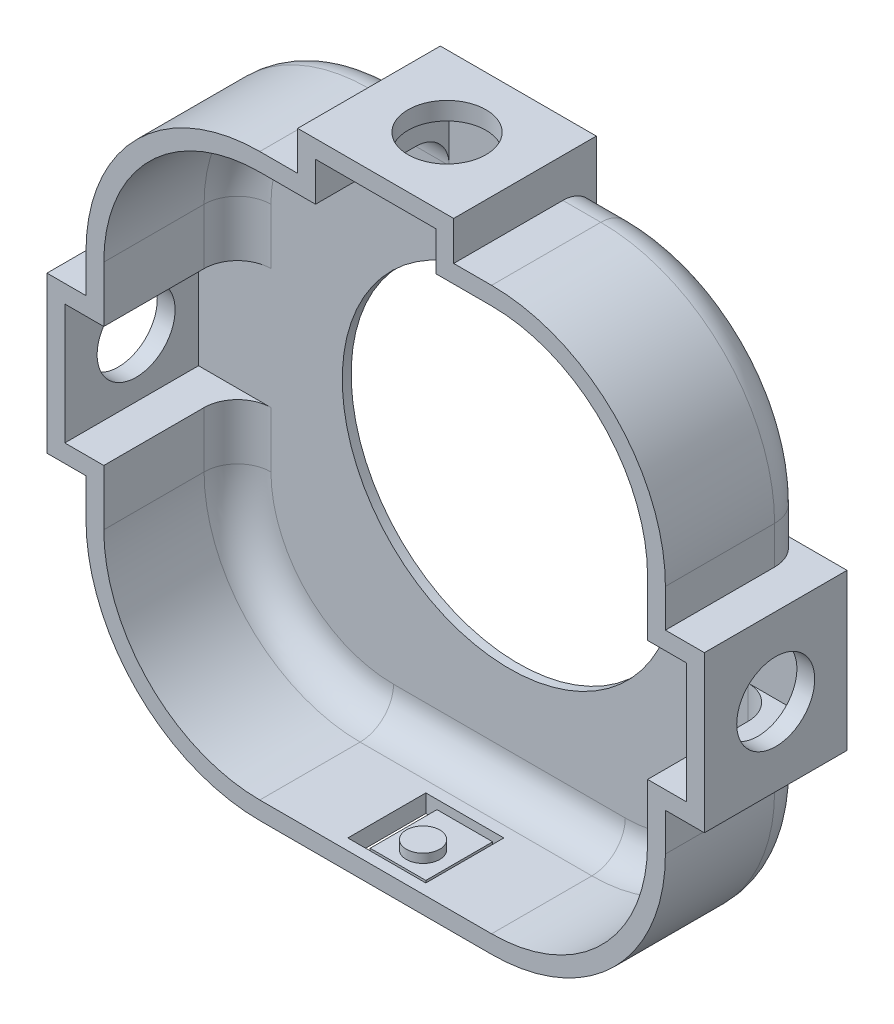
SolidWorks part; units mm, degrees
ref_plane "Спереди" through (0, 0, 0) normal (0, 0, 1) x (1, 0, 0)
ref_plane "Сверху" through (0, 0, 0) normal (0, 1, 0) x (1, 0, 0)
ref_plane "Справа" through (0, 0, 0) normal (1, 0, 0) x (0, 0, -1)
sketch "Эскиз-База" plane through (0, 0, 0) normal (0, 0, 1) x (1, 0, 0)
  line L0 (29.5, 0) -> (-29.5, 0) construction
  line L1 (-26, 26) -> (26, 26) construction
  line L2 (-26, 26) -> (-26, -26) construction
  line L3 (-26, -26) -> (26, -26) construction
  line L4 (26, 26) -> (26, -26) construction
  line L5 (-26, 26) -> (26, -26) construction
  line L6 (-26, -26) -> (26, 26) construction
  line L7 (0, -26) -> (0, 29.5) construction
  line L8 (-26, 7) -> (-29.5, 7)
  line L9 (-29.5, 7) -> (-29.5, -7)
  line L10 (-29.5, -7) -> (-26, -7)
  line L11 (26, 7) -> (29.5, 7)
  line L12 (29.5, 7) -> (29.5, -7)
  line L13 (29.5, -7) -> (26, -7)
  line L14 (-26, 10.4) -> (-26, 7)
  line L15 (-26, -10.4) -> (-26, -7)
  line L16 (-10.4, -26) -> (10.4, -26)
  line L17 (26, -10.4) -> (26, -7)
  line L18 (26, 7) -> (26, 10.4)
  line L19 (-7, 26) -> (-7, 29.5)
  line L20 (-7, 29.5) -> (7, 29.5)
  line L21 (7, 29.5) -> (7, 26)
  line L25 (-10.4, 26) -> (-7, 26)
  line L26 (7, 26) -> (10.4, 26)
  arc A0 (-26, 10.4) -> (-10.4, 26) centre (-10.4, 10.4) cw
  arc A1 (26, 10.4) -> (10.4, 26) centre (10.4, 10.4) ccw
  arc A2 (26, -10.4) -> (10.4, -26) centre (10.4, -10.4) cw
  arc A3 (-26, -10.4) -> (-10.4, -26) centre (-10.4, -10.4) ccw
  circle A4 centre (0, 0) radius 15
  point P0 (0, 0)
  point P17 (-29.5, 0)
  point P24 (29.5, 0)
  point P36 (0, 29.5)
  dimension "D2" = 15.6
  dimension "D3" = 15.6
  dimension "D5" = 59
  dimension "D6" = 14
  dimension "D8" = 30
  dimension "D1" = 52
  dimension "D4" = 14
  dimension "D7" = 29.5
extrude "Вытянуть-Стенки" add sketch "Эскиз-База" along normal blind 12 from surface thin contours A0 L25 L19 L20 L21 L26 A1 L18 L11 L12 L13 L17 A2 L16 A3 L15 L10 L9 L8 L14 starting at plane "Спереди" thin type one direction reverse wall 1.6
extrude "Бобышка-Дно" add sketch "Эскиз-База<8>" against normal blind 0.8
sketch "Эскиз-База<8>" plane through (0, 0, 0) normal (0, 0, 1) x (1, 0, 0) same geometry as "Эскиз-База"
sketch "Эскиз-Левое отверстие" plane through (-29.5, 0, 0) normal (-1, 0, 0) x (0, 0, 1)
  line L0 (-0.8, 7) -> (12, -7) construction
  line L1 (-0.8, -7) -> (12, 7) construction
  circle A0 centre (5.6, 0) radius 3.5
  dimension "D1" = 7
extrude "Вырез-Отверстия слева справа" cut sketch "Эскиз-Левое отверстие" against normal up to surface (59 mm away) up to face at (29.5, 0, 5.6)
sketch "Эскиз-Отверстие сверху" plane through (0, 29.5, 0) normal (0, 1, 0) x (1, 0, 0)
  line L0 (-7, 0.8) -> (7, -12) construction
  line L1 (-7, -12) -> (7, 0.8) construction
  circle A0 centre (0, -5.6) radius 3.5
  dimension "D1" = 7
extrude "Вырез-Верхнее отверстие" cut sketch "Эскиз-Отверстие сверху" against normal up to next
sketch "Эскиз-Кнопка записи" plane through (0, -26, 0) normal (0, -1, 0) x (1, 0, 0)
  line L0 (-10.4, 7.75) -> (10.4, 7.75) construction
  line L1 (-10.4, 12) -> (-10.4, -0.8) construction
  line L2 (10.4, 12) -> (10.4, -0.8) construction
  line L3 (50, 0) -> (-50, 0) construction
  line L4 (0, 12) -> (0, -0.8) construction
  line L5 (-10.4, 12) -> (10.4, 12) construction
  line L6 (-10.4, -0.8) -> (10.4, -0.8) construction
  line L7 (-2.5, 4) -> (-2.5, 10)
  line L8 (-2.5, 10) -> (2.5, 10)
  line L9 (3.5, 4) -> (2.5, 4)
  line L10 (3.5, 11) -> (-3.5, 11)
  line L11 (-3.5, 11) -> (-3.5, 4)
  line L12 (-3.5, 4) -> (-2.5, 4)
  line L13 (2.5, 4) -> (2.5, 10)
  line L14 (3.5, 11) -> (3.5, 4)
  line L15 (-2.5, 4) -> (2.5, 4)
  circle A0 centre (0, 7.75) radius 1.5
  point P25 (0, 10)
  point P26 (0, 11)
  dimension "D2" = 3
  dimension "D1" = 7.75
  dimension "D3" = 1
  dimension "D4" = 1
  dimension "D5" = 4
  dimension "D6" = 11
  dimension "D7" = 3.5
extrude "Вырез-Рамка кнопки" cut sketch "Эскиз-Кнопка записи" against normal up to next contours L14 L10 L11 L12 L7 L8 L13 L9 region at (-3, -26, 4.099)
extrude "Вырез-Вытянуть3" cut sketch "Эскиз-Кнопка записи<3>" against normal up to next from offset 0.8 contours L7 L15 L13 L8 A0 region at (-2.4219, -26, 7) offset against normal yes
sketch "Эскиз-Кнопка записи<3>" plane through (0, -26, 0) normal (0, -1, 0) x (1, 0, 0) same geometry as "Эскиз-Кнопка записи"
fillet "Скругление-Внутреннее" radius 3 11 edges at (-24.4, -7.9, 0) (24.4, -7.9, 0) (20.2995, -20.2995, 0) (0, -24.4, 0) (24.4, 7.9, 0) (7.9, 24.4, 0) (-7.9, 24.4, 0) (-24.4, 7.9, 0) (-20.2995, -20.2995, 0) (20.2995, 20.2995, 0) (-20.2995, 20.2995, 0)
fillet "Скругление-Наружное" radius 3 11 edges at (-26, 8.7, -0.8) (-26, -8.7, -0.8) (-21.4309, -21.4309, -0.8) (0, -26, -0.8) (21.4309, -21.4309, -0.8) (26, -8.7, -0.8) (26, 8.7, -0.8) (21.4309, 21.4309, -0.8) (8.7, 26, -0.8) (-8.7, 26, -0.8) (-21.4309, 21.4309, -0.8)
